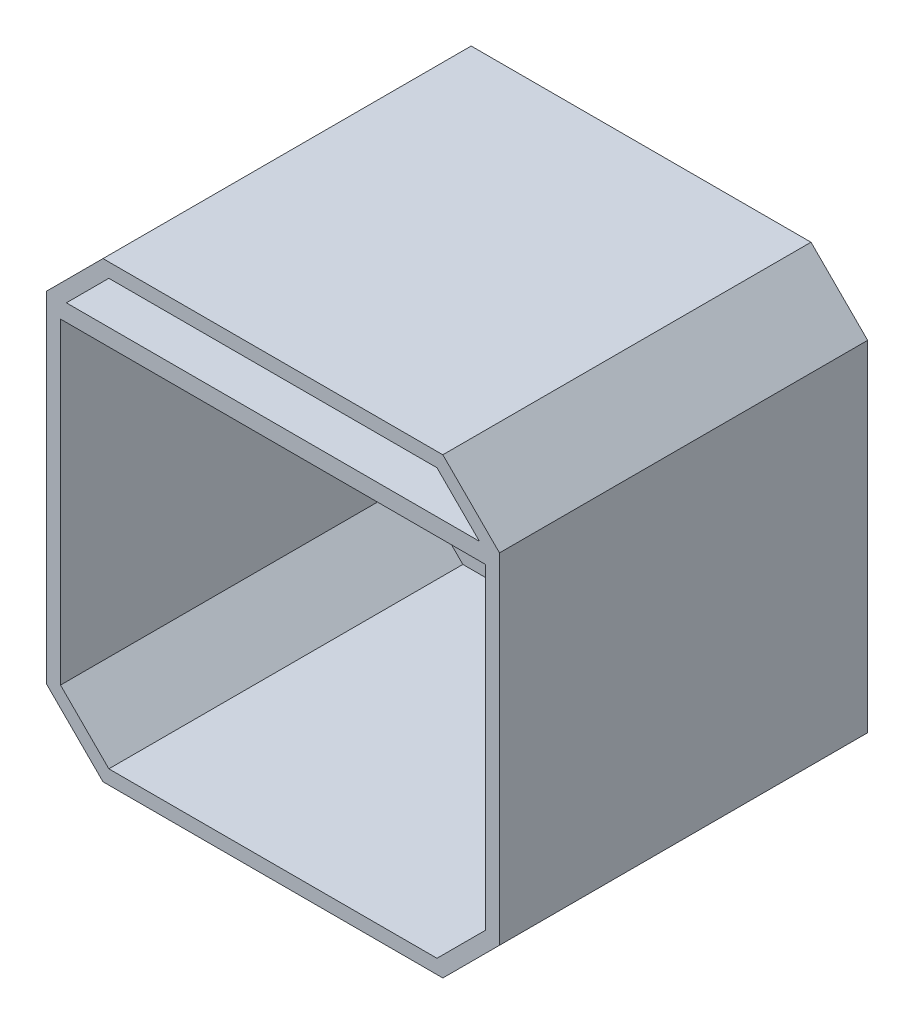
SolidWorks part; units mm, degrees
ref_plane "Front Plane" through (0, 0, 0) normal (0, 0, 1) x (1, 0, 0)
ref_plane "Top Plane" through (0, 0, 0) normal (0, 1, 0) x (1, 0, 0)
ref_plane "Right Plane" through (0, 0, 0) normal (1, 0, 0) x (0, 0, -1)
sketch "Sketch1" plane through (0, 0, 0) normal (0, 0, 1) x (1, 0, 0)
  line L0 (-40, 30) -> (-30, 40)
  line L1 (-30, -40) -> (30, -40)
  line L2 (-40, -30) -> (-40, 30)
  line L3 (-30, 40) -> (30, 40)
  line L4 (40, -30) -> (40, 30)
  line L5 (-35, -35) -> (35, 35) construction
  line L6 (-40, 40) -> (35, -35) construction
  line L7 (30, 40) -> (40, 30)
  line L8 (40, -30) -> (30, -40)
  line L9 (-30, -40) -> (-40, -30)
  line L10 (-37.5, 28.9645) -> (-28.9645, 37.5)
  line L11 (-28.9645, 37.5) -> (28.9645, 37.5)
  line L12 (28.9645, 37.5) -> (37.5, 28.9645)
  line L13 (37.5, -28.9645) -> (37.5, 28.9645)
  line L14 (37.5, -28.9645) -> (28.9645, -37.5)
  line L15 (-28.9645, -37.5) -> (28.9645, -37.5)
  line L16 (-28.9645, -37.5) -> (-37.5, -28.9645)
  line L17 (-37.5, -28.9645) -> (-37.5, 28.9645)
  line L18 (55, 0) -> (-55, 0) construction
  point P0 (0, 0)
  point P17 (0, 0)
  dimension "D1" = 2.5
  dimension "D2" = 80
  dimension "D4" = 40
  dimension "D3" = 4
extrude "Boss-Extrude1" add sketch "Sketch1" along normal blind 65
sketch "Sketch2" plane through (0, 0, 0) normal (0, 0, 1) x (1, 0, 0)
  line L0 (37.5, 28.9645) -> (28.9645, 37.5)
  line L1 (28.9645, 37.5) -> (-28.9645, 37.5)
  line L2 (-28.9645, 37.5) -> (-37.5, 28.9645)
  line L3 (-37.5, 28.9645) -> (-37.5, -28.9645)
  line L4 (-37.5, -28.9645) -> (-28.9645, -37.5)
  line L5 (-28.9645, -37.5) -> (28.9645, -37.5)
  line L6 (28.9645, -37.5) -> (37.5, -28.9645)
  line L7 (37.5, -28.9645) -> (37.5, 28.9645)
  circle A0 centre (0, 0) radius 7.5
  dimension "D1" = 15
extrude "Boss-Extrude2" add sketch "Sketch2" along normal blind 2.5
sketch "Sketch3" plane through (0, 0, 0) normal (1, 0, 0) x (0, 0, -1)
  line L0 (0, 55) -> (0, -55) construction
  line L1 (-65, 30) -> (0, 30)
  line L2 (-65, 30) -> (-65, 27)
  line L3 (-65, 27) -> (0, 27)
  line L4 (0, 30) -> (0, 27)
  dimension "D1" = 3
extrude "Boss-Extrude3" add sketch "Sketch3" along normal up to next and the other way up to next
sketch "Sketch5" plane through (0, 0, 65) normal (0, 0, 1) x (1, 0, 0)
  line L0 (-37.5, 27) -> (37.5, 27) construction
  line L1 (7.5, 27) -> (-37.5, 27)
  line L2 (7.5, 27) -> (7.5, 30)
  line L3 (7.5, 30) -> (-37.5, 30)
  line L4 (-37.5, 27) -> (-37.5, 30)
  line L6 (-37.5, 27) -> (-37.5, -28.9645) construction
  line L7 (-36.4645, 30) -> (36.4645, 30) construction
  dimension "D1" = 45
extrude "Boss-Extrude4" [suppressed] add sketch "Sketch5" along normal blind 12.5
sketch "Sketch4" [suppressed] plane through (0, 27, 0) normal (0, -1, 0) x (1, 0, 0)
  line L1 (-37.5, 2.5) -> (-37.5, 50) construction
  line L2 (-37.5, 62.5) -> (7.5, 62.5) construction
  circle A0 centre (-27.5, 22.5) radius 1.75
  circle A1 centre (2.5, 57.5) radius 1.75
  dimension "D1" = 3.5
  dimension "D2" = 3.5
  dimension "D3" = 30
  dimension "D4" = 35
  dimension "D5" = 5
  dimension "D6" = 10
extrude "Cut-Extrude1" [suppressed] cut sketch "Sketch4" against normal up to next
sketch "Sketch6" plane through (0, 27, -27) normal (0, -1, 0) x (-1, 0, 0)
  line L1 (-37.5, -29.5) -> (37.5, -29.5) construction
  line L3 (37.5, -29.5) -> (37.5, -92) construction
  circle A0 centre (0, -72) radius 1.75
  circle A1 centre (30, -37) radius 1.75
  dimension "D1" = 3.5
  dimension "D2" = 3.5
  dimension "D3" = 30
  dimension "D4" = 35
  dimension "D5" = 7.5
  dimension "D6" = 7.5
extrude "Cut-Extrude2" cut sketch "Sketch6" against normal up to next
sketch "Sketch7" plane through (0, 0, 2.5) normal (0, 0, 1) x (1, 0, 0)
  line L0 (-36.4645, 30) -> (-28.9645, 37.5)
  line L1 (-28.9645, 37.5) -> (-36.4645, 30) construction
  line L2 (-28.9645, 37.5) -> (28.9645, 37.5)
  line L3 (28.9645, 37.5) -> (36.4645, 30)
  line L4 (36.4645, 30) -> (-36.4645, 30)
extrude "Cut-Extrude3" cut sketch "Sketch7" against normal up to next
sketch "Sketch8" plane through (0, 0, 2.5) normal (0, 0, 1) x (1, 0, 0)
  line L6 (-15, 8) -> (-15, 3.3963) construction
  line L7 (-37.5, 27) -> (37.5, 27) construction
  line L9 (-5, 7.5) -> (0, 7.5)
  line L10 (0, 7.5) -> (-7.5, 0)
  line L11 (35.75, 0) -> (-35.75, 0) construction
  line L13 (-25, 17) -> (-5, 17)
  line L14 (-25, 17) -> (-25, 8)
  line L15 (-25, 8) -> (-15, 8)
  line L16 (-5, 17) -> (-5, 7.5)
  line L18 (-19.75, 10.36) -> (-10.25, 10.36) construction
  circle A0 centre (0, 0) radius 7.5 construction
  circle A1 centre (0, 0) radius 7.5 construction
  arc A2 (-15, 8) -> (-7.5, 0) centre (-15.25, 0.25) cw
  point P16 (-15, 10.36)
  dimension "D1" = 10
  dimension "D2" = 10
  dimension "D3" = 0
  dimension "D6" = 20
  dimension "D7" = 9
extrude "Cut-Extrude4" cut sketch "Sketch8" against normal up to next
fillet "Fillet1" radius 2.5 3 edges at (-5, 17, 1.25) (-25, 17, 1.25) (-25, 8, 1.25)
fillet "Fillet2" radius 5 1 edges at (-5, 7.5, 1.25)
